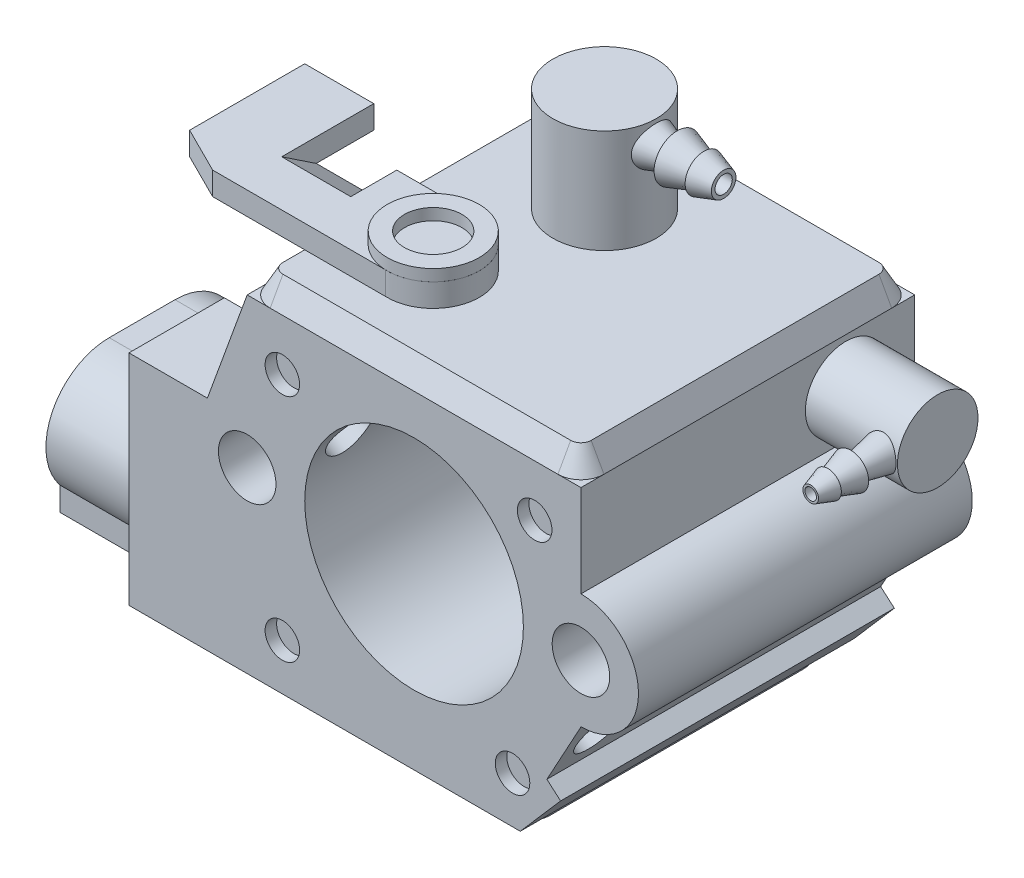
SolidWorks part; units mm, degrees
ref_plane "Front Plane" through (0, 0, 0) normal (0, 0, 1) x (1, 0, 0)
ref_plane "Top Plane" through (0, 0, 0) normal (0, 1, 0) x (1, 0, 0)
ref_plane "Right Plane" through (0, 0, 0) normal (1, 0, 0) x (0, 0, -1)
sketch "Sketch1" plane through (0, 0, 0) normal (0, 0, 1) x (1, 0, 0)
  line L0 (-14.0288, 0) -> (19.9712, 0)
  line L1 (-14.0288, 0) -> (-14.0288, 19)
  line L2 (-14.0288, 19) -> (-7.2131, 19)
  line L3 (-7.2131, 19) -> (-3.7554, 28.5)
  line L4 (-3.7554, 28.5) -> (25.2446, 28.5)
  line L5 (25.2446, 28.5) -> (25.2446, 20.5)
  line L6 (19.9712, 0) -> (23.4763, 4.0361)
  line L9 (23.4763, 4.0361) -> (22.2866, 5.0693)
  line L10 (22.2866, 5.0693) -> (25.2505, 10.5)
  line L11 (23.7685, 7.7847) -> (-5.4842, 23.75) construction
  circle A0 centre (25.2446, 15.5) radius 2.5
  arc A1 (25.2505, 10.5) -> (25.2446, 20.5) centre (25.2446, 15.5) ccw
  circle A2 centre (25.2446, 15.5) radius 5 construction
  dimension "D9" = 5
  dimension "D10" = 5
  dimension "D1" = 34
  dimension "D2" = 19
  dimension "D3" = 8
  dimension "D4" = 70
  dimension "D5" = 9.5
  dimension "D6" = 29
  dimension "D7" = 19.9712
  dimension "D8" = 23.4763
  dimension "D11" = 22.2866
  dimension "D12" = 25.2446
  dimension "D14" = 4.0361
extrude "Boss-Extrude1" add sketch "Sketch1" along normal blind 29 contours A1 L5 L4 L3 L2 L1 L0 L6 A0 region at (6.8323, 13.755, 0)
sketch "Sketch2" plane through (0, 0, 29) normal (0, 0, 1) x (1, 0, 0)
  line L0 (28.9539, 15.5) -> (-14.0288, 15.5) construction
  line L2 (-3.7554, 28.5) -> (25.2446, 28.5) construction
  line L3 (25.2446, 28.5) -> (25.2446, 20.5) construction
  line L6 (-14.0288, 0) -> (-14.0288, 19) construction
  circle A0 centre (10.7446, 15.5) radius 9.5
  circle A1 centre (-3.7554, 15.5) radius 2.5
  circle A2 centre (21.2253, 24.0361) radius 1.5
  circle A3 centre (-0.6982, 24.0361) radius 1.5
  circle A4 centre (19.3018, 4.0361) radius 1.5
  circle A5 centre (-0.6982, 4.0361) radius 1.5
  circle A6 centre (25.2446, 15.5) radius 2.5 construction
  circle A7 centre (25.2446, 15.5) radius 2.5 construction
  dimension "D1" = 19
  dimension "D2" = 5
  dimension "D7" = 3
  dimension "D10" = 4.4639
  dimension "D3" = 14.5
  dimension "D4" = 5.9429
  dimension "D5" = 20
  dimension "D6" = 20
  dimension "D8" = 14.5
  dimension "D9" = 4.0193
extrude "Cut-Extrude1" cut sketch "Sketch2" against normal through all contours A0
extrude "Cut-Extrude2" cut sketch "Sketch2<6>" against normal blind 1
sketch "Sketch2<6>" plane through (0, 0, 29) normal (0, 0, 1) x (1, 0, 0) same geometry as "Sketch2"
sketch "Sketch6" plane through (0, 0, 28) normal (0, 0, 1) x (1, 0, 0)
  line L0 (27.7446, 15.5) -> (-15.4439, 15.5) construction
  line L1 (25.2446, 18) -> (25.2446, 13) construction
  line L2 (10.7446, 15.5) -> (10.7446, 35.1279) construction
  line L3 (10.7446, 15.5) -> (10.7446, -5.7586) construction
  circle A0 centre (25.2446, 15.5) radius 2.5 construction
  circle A1 centre (-3.7554, 15.5) radius 2.5
  circle A3 centre (25.2446, 15.5) radius 2.5
  circle A4 centre (10.7446, 15.5) radius 9.5 construction
  circle A5 centre (10.7446, 15.5) radius 9.5
  dimension "D2" = 5
  dimension "D1" = 29
extrude "Cut-Extrude3" cut sketch "Sketch6" against normal through all
sketch "Sketch7" plane through (-12.4758, 4.5408, 0) normal (-0.9397, 0.342, 0) x (0, 0, 1)
  line L0 (29, 15.3871) -> (29, 25.4968) construction
  line L1 (29, 25.4968) -> (0, 25.4968) construction
  circle A0 centre (25, 20.9968) radius 2.5
  circle A1 centre (7, 20.9968) radius 2.5
  dimension "D1" = 5
  dimension "D2" = 4
  dimension "D3" = 18
  dimension "D4" = 4.5
  dimension "D5" = 4.5
sketch "Sketch8" plane through (15.0399, -8.2084, 0) normal (0.8778, -0.4791, 0) x (0, 0, -1)
  line L0 (-29, 21.3133) -> (0, 21.3133) construction
  line L1 (0, 15.1265) -> (0, 21.3133) construction
  circle A0 centre (-22.5, 17.3133) radius 2.5
  circle A1 centre (-4.5, 17.3133) radius 2.5
  dimension "D1" = 5
  dimension "D4" = 5
  dimension "D2" = 4
  dimension "D3" = 4.5
  dimension "D5" = 4
  dimension "D6" = 18
sketch "Sketch27" plane through (15.0399, -8.2084, 0) normal (0.8778, -0.4791, 0) x (0, 0, -1)
  line L0 (-29, 15.1265) -> (-29, 21.3133) construction
  line L1 (-29, 21.3133) -> (0, 21.3133) construction
  circle A0 centre (-26, 18.3133) radius 2
  circle A1 centre (-4, 18.3133) radius 2
  dimension "D1" = 4
  dimension "D4" = 4
  dimension "D2" = 3
  dimension "D3" = 3
  dimension "D5" = 22
  dimension "D6" = 3
extrude "Cut-Extrude7" cut sketch "Sketch27" against normal blind 65
sketch "Sketch10" plane through (-14.0288, 0, 0) normal (-1, 0, 0) x (0, 0, 1)
  line L0 (11, 0) -> (25, 0)
  line L5 (29, 0) -> (0, 0) construction
  line L6 (20.7143, 11) -> (15, 11)
  line L7 (0, 0) -> (0, 19) construction
  line L8 (25, 0) -> (25, 2.0529)
  line L9 (11, 0) -> (11, 1.7251)
  arc A4 (17.8571, 3.4784) -> (17.8571, 7.5216) centre (20.7143, 5.5) ccw
  arc A5 (17.8571, 7.5216) -> (17.8571, 3.4784) centre (15, 5.5) ccw
  arc A6 (15, 11) -> (11, 1.7251) centre (15, 5.5) ccw
  arc A7 (25, 2.0529) -> (20.7143, 11) centre (20.7143, 5.5) ccw
  circle A9 centre (20.7143, 5.5) radius 3.5 construction
  circle A10 centre (20.7143, 5.5) radius 5.5 construction
  dimension "D2" = 14
  dimension "D5" = 7
  dimension "D4" = 7
  dimension "D6" = 5.5
  dimension "D7" = 5.5
  dimension "D8" = 2.0529
  dimension "D1" = 11
  dimension "D3" = 4
  dimension "D9" = 5.5
  dimension "D10" = 15
extrude "Boss-Extrude2" add sketch "Sketch10" along normal blind 10
sketch "Sketch11" plane through (-14.0288, 0, 0) normal (-1, 0, 0) x (0, 0, 1)
  line L0 (9.5, 5.5) -> (9.5, 19)
  line L1 (20.7143, 11) -> (20.7143, 19)
  line L2 (20.7143, 19) -> (20.7143, 20)
  line L3 (20.7143, 20) -> (9.5, 20)
  line L4 (9.5, 20) -> (9.5, 19)
  line L5 (20.7143, 11) -> (15, 11) construction
  line L8 (11, 0) -> (11, 1.7251)
  line L9 (15, 11) -> (20.7143, 11)
  line L10 (25, 2.0529) -> (25, 0)
  line L11 (25, 0) -> (29, 0)
  line L12 (29, 0) -> (29, 19)
  line L13 (29, 19) -> (0, 19)
  line L14 (0, 19) -> (0, 0)
  line L15 (0, 0) -> (11, 0)
  line L17 (15, 11) -> (20.7143, 11)
  arc A2 (15, 11) -> (11, 1.7251) centre (15, 5.5) ccw
  arc A3 (25, 2.0529) -> (20.7143, 11) centre (20.7143, 5.5) ccw
  arc A4 (15, 11) -> (9.5, 5.5) centre (15, 5.5) ccw
  dimension "D2" = 1
  dimension "D3" = 8
  dimension "D1" = 0
extrude "Cut-Extrude4" cut sketch "Sketch11" against normal blind 7
sketch "Sketch12" plane through (0, 0, 0) normal (0, -1, 0) x (1, 0, 0)
  line L0 (-14.0288, 0) -> (19.9712, 0) construction
  line L1 (-5.9288, 27.5) -> (17.0712, 27.5)
  line L2 (-7.9288, 25.5) -> (-7.9288, 3.5)
  line L3 (-5.9288, 1.5) -> (17.0712, 1.5)
  line L4 (19.0712, 25.5) -> (19.0712, 3.5)
  line L5 (-7.9288, 27.5) -> (19.0712, 1.5) construction
  line L6 (-7.9288, 1.5) -> (19.0712, 27.5) construction
  line L7 (19.9712, 29) -> (19.9712, 0) construction
  arc A0 (17.0712, 1.5) -> (19.0712, 3.5) centre (17.0712, 3.5) ccw
  arc A1 (-5.9288, 27.5) -> (-7.9288, 25.5) centre (-5.9288, 25.5) ccw
  arc A2 (17.0712, 27.5) -> (19.0712, 25.5) centre (17.0712, 25.5) cw
  arc A3 (-7.9288, 3.5) -> (-5.9288, 1.5) centre (-5.9288, 3.5) ccw
  point P0 (5.5712, 14.5)
  dimension "D5" = 2
  dimension "D1" = 27
  dimension "D2" = 26
  dimension "D3" = 14.5
  dimension "D4" = 14.4
extrude "Boss-Extrude3" add sketch "Sketch12" along normal blind 1
sketch "Sketch13" plane through (0, -1, 0) normal (0, -1, 0) x (1, 0, 0)
  line L0 (17.0712, 27.5) -> (-5.9288, 27.5) construction
  line L1 (19.0712, 3.5) -> (19.0712, 25.5) construction
  circle A0 centre (5.5712, 14.5) radius 10.5
  dimension "D3" = 21
  dimension "D1" = 13
  dimension "D2" = 13.5
extrude "Boss-Extrude4" add sketch "Sketch13" along normal blind 1.5 draft 36
sketch "Sketch14" plane through (25.2446, 0, 0) normal (1, 0, 0) x (0, 0, -1)
  line L0 (-29, 28.5) -> (0, 28.5) construction
  line L1 (0, 28.5) -> (0, 20.5) construction
  circle A0 centre (-6, 24.5) radius 3.5
  dimension "D1" = 7
  dimension "D2" = 4
  dimension "D3" = 6
extrude "Boss-Extrude5" add sketch "Sketch14" along normal blind 8
sketch "Sketch15" plane through (33.2446, 0, 0) normal (1, 0, 0) x (0, 0, -1)
  line L0 (-2.5, 24.5) -> (-9.5, 24.5) construction
  circle A0 centre (-6, 24.5) radius 3.5 construction
ref_plane "Plane2" through (0, 24.5, 0) normal (0, 1, 0) x (0, 0, 1)
sketch "Sketch16" plane through (0, 24.5, 0) normal (0, 1, 0) x (0, 0, 1)
  line L0 (8.8789, 33.2446) -> (12, 32.5978)
  line L1 (2.5, 33.2446) -> (9.5, 33.2446) construction
  line L2 (12, 32.5978) -> (12, 33.2446)
  line L3 (12, 33.2446) -> (14, 32.5978)
  line L4 (14, 32.5978) -> (14, 32.8715)
  line L5 (14, 32.8715) -> (15.5, 32.3863)
  line L6 (15.5, 32.3863) -> (15.5, 31.7077)
  line L7 (15.5, 31.7077) -> (9.5, 31.7077)
  line L8 (9.5, 25.2446) -> (9.5, 33.2446) construction
  line L9 (8.8789, 31.7077) -> (8.8789, 33.2446)
  line L10 (9.5, 31.7077) -> (8.8789, 31.7077)
  dimension "D1" = 8.8789
  dimension "D2" = 12
  dimension "D3" = 14
  dimension "D4" = 15.5
  dimension "D5" = 31.7077
  dimension "D6" = 32.3863
  dimension "D7" = 32.5978
revolve "Revolve1" add sketch "Sketch16" angle 360 about L7
sketch "Sketch17" plane through (0, 28.5, 0) normal (0, 1, 0) x (1, 0, 0)
  line L4 (25.2446, 0) -> (-3.7554, 0)
  line L5 (-3.7554, 0) -> (-3.7554, -29)
  line L6 (-3.7554, -29) -> (25.2446, -29)
  line L7 (25.2446, -29) -> (25.2446, 0)
  line L8 (23.2446, 0) -> (-1.7554, 0)
  line L9 (-3.7554, -2) -> (-3.7554, -27)
  line L10 (-1.7554, -29) -> (23.2446, -29)
  line L11 (25.2446, -27) -> (25.2446, -2)
  arc A0 (23.2446, 0) -> (25.2446, -2) centre (23.2446, -2) cw
  arc A1 (23.2446, -29) -> (25.2446, -27) centre (23.2446, -27) ccw
  arc A2 (-3.7554, -27) -> (-1.7554, -29) centre (-1.7554, -27) ccw
  arc A3 (-1.7554, 0) -> (-3.7554, -2) centre (-1.7554, -2) ccw
  dimension "D2" = 2
  dimension "D1" = 0
extrude "Boss-Extrude6" add sketch "Sketch17" along normal blind 2 draft 29
sketch "Sketch18" plane through (0, 30.5, 0) normal (0, 1, 0) x (1, 0, 0)
  circle A0 centre (7.2674, -8.9711) radius 4.4914
extrude "Boss-Extrude7" add sketch "Sketch18" along normal blind 9
sketch "Sketch19" plane through (0, 30.5, 0) normal (0, 1, 0) x (1, 0, 0)
  line L8 (-10.6467, -25.1086) -> (-14.6467, -23.1086)
  line L9 (-2.6467, -25.1086) -> (4.3533, -25.1086)
  line L10 (-2.6467, -2) -> (-2.6467, -27) construction
  line L11 (-2.6467, -17.1086) -> (4.6872, -17.1086)
  line L12 (-2.6467, -25.1086) -> (-10.6467, -25.1086)
  line L13 (-14.6467, -23.1086) -> (-14.6467, -13.1086)
  line L14 (-14.6467, -13.1086) -> (-8.6467, -13.1086)
  line L15 (-8.6467, -13.1086) -> (-8.6467, -23.1086)
  line L16 (-8.6467, -23.1086) -> (-2.6467, -23.1086)
  line L17 (-2.6467, -23.1086) -> (-2.6467, -17.1086)
  line L18 (23.2446, -1.1086) -> (-1.7554, -1.1086) construction
  arc A1 (4.6872, -17.1086) -> (4.3533, -25.1086) centre (4.5202, -21.1086) cw
  point P18 (-14.6467, -25.1086)
  dimension "D15" = 4.0035
  dimension "D2" = 20
  dimension "D3" = 4
  dimension "D4" = 2
  dimension "D9" = 8
  dimension "D10" = 6
  dimension "D11" = 6
  dimension "D12" = 2
  dimension "D13" = 7
  dimension "D14" = 16
  dimension "D16" = 12
extrude "Boss-Extrude8" add sketch "Sketch19" along normal blind 2
sketch "Sketch20" plane through (0, 32.5, 0) normal (0, 1, 0) x (1, 0, 0)
  circle A0 centre (4.5202, -21.1086) radius 2.5
  circle A1 centre (4.5202, -21.1086) radius 4
  dimension "D1" = 5
  dimension "D2" = 8
extrude "Boss-Extrude9" add sketch "Sketch20" along normal blind 1
sketch "Sketch21" plane through (0, 39.5, 0) normal (0, 1, 0) x (1, 0, 0)
  line L0 (11.7588, -8.9711) -> (2.7761, -8.9711) construction
  circle A0 centre (7.2674, -8.9711) radius 4.4914 construction
ref_plane "Plane3" through (0, 0, 8.9711) normal (0, 0, -1) x (-1, 0, 0)
sketch "Sketch22" plane through (0, 0, 8.9711) normal (0, 0, -1) x (-1, 0, 0)
  line L1 (-11.7588, 39.5) -> (-2.7761, 39.5) construction
  line L7 (-17.6153, 37.4905) -> (-10.7363, 37.4905)
  line L8 (-10.7363, 37.4905) -> (-10.7363, 39.5)
  line L9 (-10.7363, 39.5) -> (-13.5786, 38.5589)
  line L10 (-13.5786, 38.5589) -> (-13.5786, 39.5)
  line L11 (-13.5786, 39.5) -> (-15.8932, 38.7336)
  line L12 (-15.8932, 38.7336) -> (-15.8932, 39.1168)
  line L13 (-15.8932, 39.1168) -> (-17.6153, 38.5589)
  line L14 (-17.6153, 38.5589) -> (-17.6153, 37.4905)
  dimension "D1" = 10.7363
  dimension "D2" = 13.5786
  dimension "D3" = 15.8932
  dimension "D4" = 17.6153
  dimension "D5" = 37.4905
  dimension "D6" = 38.5589
  dimension "D8" = 39.1168
revolve "Revolve2" add sketch "Sketch22" angle 360 about L7
sketch "Sketch24" plane through (-8.6467, 0, 0) normal (1, 0, 0) x (0, 0, -1)
  line L0 (-21.1086, 32.5) -> (-18.1086, 30.5)
  line L1 (-23.1086, 32.5) -> (-13.1086, 32.5) construction
  line L2 (-23.1086, 30.5) -> (-13.1086, 30.5) construction
  line L3 (-18.1086, 30.5) -> (-23.1086, 30.5)
  line L4 (-23.1086, 30.5) -> (-23.1086, 32.5)
  line L5 (-23.1086, 32.5) -> (-21.1086, 32.5)
  dimension "D1" = 8
  dimension "D2" = 5
extrude "Boss-Extrude10" add sketch "Sketch24" along normal up to body separate body
sketch "Sketch25" plane through (0, 0, 15.5) normal (0, 0, 1) x (1, 0, 0)
  circle A0 centre (31.7077, 24.5) radius 0.5
  dimension "D1" = 1
extrude "Cut-Extrude5" cut sketch "Sketch25" against normal blind 9
sketch "Sketch26" plane through (17.6153, 0, 0) normal (1, 0, 0) x (0, 0, -1)
  circle A0 centre (-8.9711, 37.4905) radius 0.75
  dimension "D1" = 1.5
extrude "Cut-Extrude6" cut sketch "Sketch26" against normal blind 9
